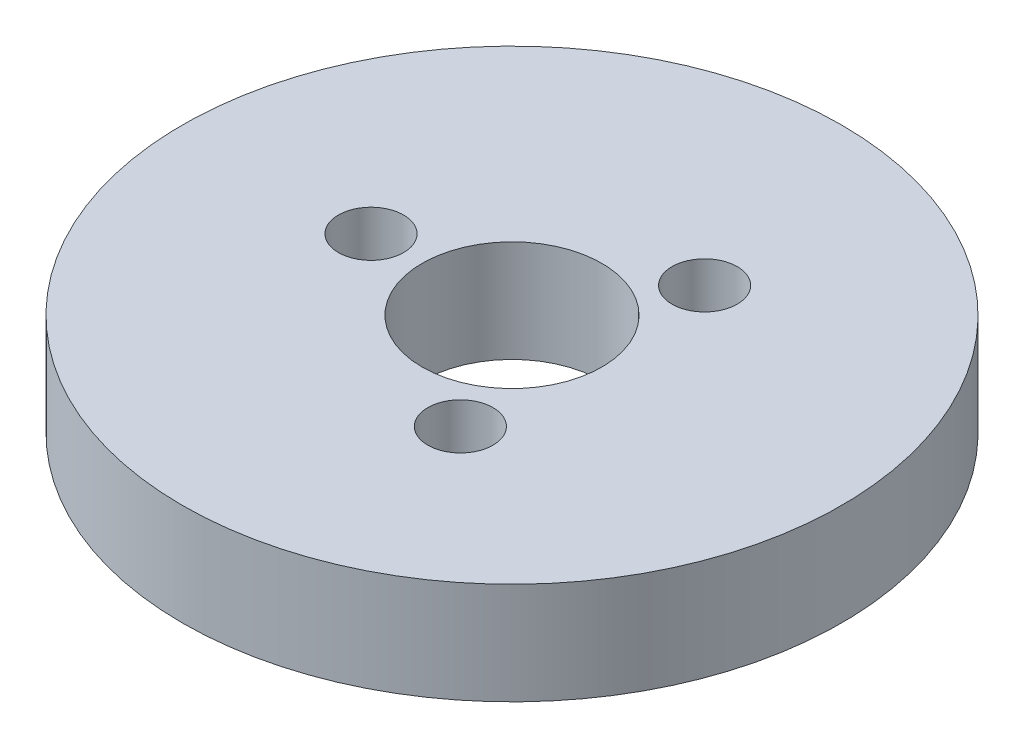
SolidWorks part; units mm, degrees
ref_plane "Front Plane" through (0, 0, 0) normal (0, 0, 1) x (1, 0, 0)
ref_plane "Top Plane" through (0, 0, 0) normal (0, 1, 0) x (1, 0, 0)
ref_plane "Right Plane" through (0, 0, 0) normal (1, 0, 0) x (0, 0, -1)
sketch "Sketch1" plane through (0, 0, 0) normal (0, 1, 0) x (1, 0, 0)
  circle A0 centre (0, 0) radius 55
  dimension "FLANGE_OD" = 110
extrude "Boss-Extrude1" add sketch "Sketch1" along normal blind 17
sketch "Sketch2" plane through (0, 0, 0) normal (0, 1, 0) x (1, 0, 0)
  circle A0 centre (0, 0) radius 15
  dimension "BORE_D" = 30
extrude "Cut-Extrude1" cut sketch "Sketch2" along normal through all
sketch "Sketch3" plane through (0, 17, 0) normal (0, 1, 0) x (1, 0, 0)
  circle A0 centre (0, 0) radius 23.5316 construction
  circle A1 centre (-23.5316, 0) radius 5.4402
  dimension "BOLT_D" = 10.8803
  dimension "BOLT_PCD" = 47.0632
extrude "Cut-Extrude2" cut sketch "Sketch3" against normal blind 13.1578
pattern_circular "CirPattern1" count 3 over 360 about axis through (0, 0, 0) along (0, 1, 0) of "Cut-Extrude2"
